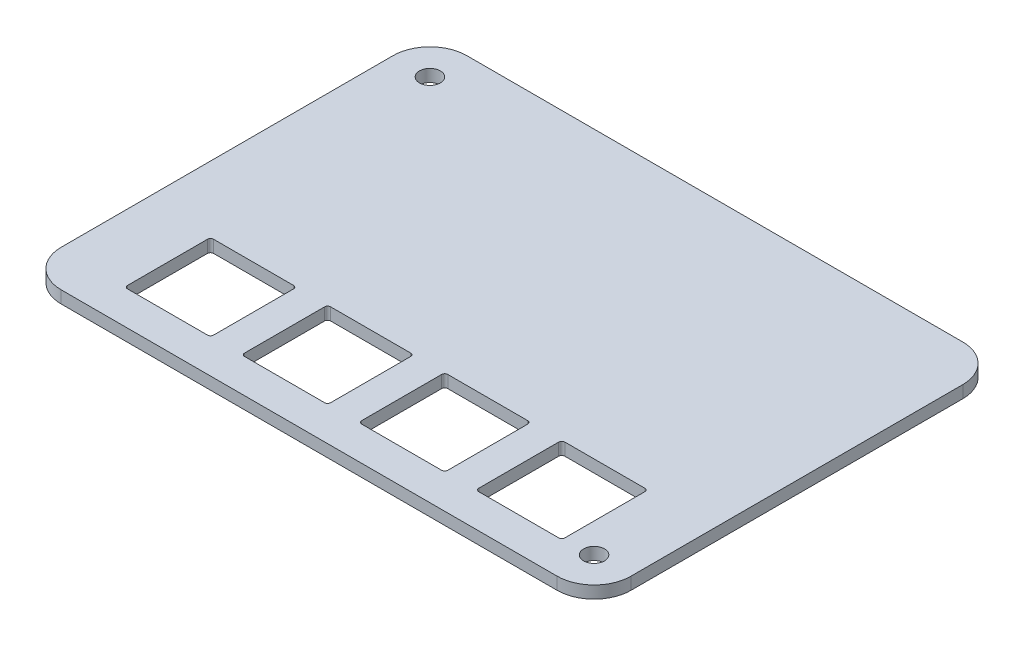
SolidWorks part; units mm, degrees
note: The reader was unsure of these and kept them because the rebuilt part matched: shared geometry of "Schizzo5<3>".
ref_plane "Piano frontale" through (0, 0, 0) normal (0, 0, 1) x (1, 0, 0)
ref_plane "Piano superiore" through (0, 0, 0) normal (0, 1, 0) x (1, 0, 0)
ref_plane "Piano destro" through (0, 0, 0) normal (1, 0, 0) x (0, 0, -1)
sketch "Schizzo1" plane through (0, 0, 0) normal (0, 1, 0) x (1, 0, 0)
  line L0 (0, 0) -> (0, 60)
  line L5 (0, 60) -> (-76.2, 60)
  line L6 (-76.2, 60) -> (-76.2, 0)
  line L8 (8.2513, -3) -> (-84.4513, -3)
  line L9 (8.2513, -3) -> (8.2513, 63)
  line L10 (8.2513, 63) -> (-84.4513, 63)
  line L11 (-84.4513, -3) -> (-84.4513, 63)
  line B0 (-76.2, 0) -> (0, 0)
  line B1 (-76.2, 19.05) -> (0, 19.05)
  line B2 (-73.175, 16.525) -> (-60.175, 16.525)
  line B3 (-73.175, 2.525) -> (-60.175, 2.525)
  line B4 (-73.675, 16.025) -> (-73.675, 3.025)
  line B5 (-59.675, 16.025) -> (-59.675, 3.025)
  line B6 (-54.125, 16.525) -> (-41.125, 16.525)
  line B7 (-54.125, 2.525) -> (-41.125, 2.525)
  line B8 (-54.625, 16.025) -> (-54.625, 3.025)
  line B9 (-40.625, 16.025) -> (-40.625, 3.025)
  line B10 (-35.075, 16.525) -> (-22.075, 16.525)
  line B11 (-35.075, 2.525) -> (-22.075, 2.525)
  line B12 (-35.575, 16.025) -> (-35.575, 3.025)
  line B13 (-21.575, 16.025) -> (-21.575, 3.025)
  line B14 (-16.025, 16.525) -> (-3.025, 16.525)
  line B15 (-16.025, 2.525) -> (-3.025, 2.525)
  line B16 (-16.525, 16.025) -> (-16.525, 3.025)
  line B17 (-2.525, 16.025) -> (-2.525, 3.025)
  line B18 (-76.2, 0) -> (-76.2, 19.05)
  line B19 (0, 0) -> (0, 19.05)
  arc B20 (-73.175, 16.525) -> (-73.675, 16.025) centre (-73.175, 16.025) ccw
  arc B21 (-59.675, 16.025) -> (-60.175, 16.525) centre (-60.175, 16.025) ccw
  arc B22 (-73.675, 3.025) -> (-73.175, 2.525) centre (-73.175, 3.025) ccw
  arc B23 (-60.175, 2.525) -> (-59.675, 3.025) centre (-60.175, 3.025) ccw
  arc B24 (-54.125, 16.525) -> (-54.625, 16.025) centre (-54.125, 16.025) ccw
  arc B25 (-40.625, 16.025) -> (-41.125, 16.525) centre (-41.125, 16.025) ccw
  arc B26 (-54.625, 3.025) -> (-54.125, 2.525) centre (-54.125, 3.025) ccw
  arc B27 (-41.125, 2.525) -> (-40.625, 3.025) centre (-41.125, 3.025) ccw
  arc B28 (-35.075, 16.525) -> (-35.575, 16.025) centre (-35.075, 16.025) ccw
  arc B29 (-21.575, 16.025) -> (-22.075, 16.525) centre (-22.075, 16.025) ccw
  arc B30 (-35.575, 3.025) -> (-35.075, 2.525) centre (-35.075, 3.025) ccw
  arc B31 (-22.075, 2.525) -> (-21.575, 3.025) centre (-22.075, 3.025) ccw
  arc B32 (-16.025, 16.525) -> (-16.525, 16.025) centre (-16.025, 16.025) ccw
  arc B33 (-2.525, 16.025) -> (-3.025, 16.525) centre (-3.025, 16.025) ccw
  arc B34 (-16.525, 3.025) -> (-16.025, 2.525) centre (-16.025, 3.025) ccw
  arc B35 (-3.025, 2.525) -> (-2.525, 3.025) centre (-3.025, 3.025) ccw
  dimension "D1" = 40.95
  dimension "D2" = 3
  dimension "D3" = 8.2513
  dimension "D4" = 3
  dimension "D5" = 8.2513
sketch_block_instance "plate-2026-10-07T17_50_42.415Z-1"
sketch_block "plate-2026-10-07T17_50_42.415Z"
extrude "Estrusione-Estrusione1" add sketch "Schizzo1" along normal blind 2 contours L6 B1 L0 L5 | B1 L6 B0 L0 B35 B15 B34 B16 B32 B14 B33 B17 B31 B11 B30 B12 B28 B10 B29 B13 B27 B7 B26 B8 B24 B6 B25 B9 B23 B3 B22 B4 B20 B2 B21 B5 | L11 L8 L9 L10 B0 L6 L5 L0
fillet "Raccordo1" radius 6 4 edges at (-84.4513, 1, 3) (8.2513, 1, 3) (8.2513, 1, -63) (-84.4513, 1, -63)
sketch "Schizzo2" plane through (0, 2, 0) normal (0, 1, 0) x (1, 0, 0)
  arc A2 (-78.4513, 63) -> (-84.4513, 57) centre (-78.4513, 57) ccw construction
  arc A3 (2.2513, -3) -> (8.2513, 3) centre (2.2513, 3) ccw construction
  point P0 (-78.4513, 57)
  point P2 (2.2513, 3)
  point P8 (0, 0)
  point P12 (0, 0)
  point P13 (0, 0)
  point P17 (0, 0)
  point P18 (0, 0)
hole_wizard "Foro per Vite M3-1" positions "Schizzo2" profile "Schizzo3" hole size "M3" standard "ISO"
sketch "Schizzo3" plane through (-78.4513, 2, -57) normal (1, 0, 0) x (0, 0, 1)
  line L0 (0, 0) -> (0, 14.0215)
  line L1 (0, 14.0215) -> (1.7, 13)
  line L2 (1.7, 13) -> (1.7, 0)
  line L5 (1.7, 0) -> (0, 0)
  line L10 (0, 14.0215) -> (-1.7, 13) construction
  line L11 (0, -6.35) -> (0, 107.95) construction
  dimension "Hole Dia." = 3.4
  dimension "Hole Depth" = 13
  dimension "Drill Angle" = 118
sketch "Schizzo5" plane through (0, 0, 0) normal (0, 1, 0) x (1, 0, 0)
  line L0 (-48.9354, 27.1805) -> (-52.2996, 33.9829)
  line L1 (-52.2996, 33.9829) -> (-53.1758, 36.2114)
  line L2 (-53.1758, 36.2114) -> (-53.1758, 36.5924)
  line L3 (-53.1758, 36.5924) -> (-52.2615, 37.44)
  line L4 (-46.252, 47.7543) -> (-48.6235, 50.4971)
  line L5 (-48.6235, 50.4971) -> (-49.5568, 51.6305)
  line L6 (-49.5568, 51.6305) -> (-49.8425, 51.859)
  line L7 (-49.8425, 51.859) -> (-49.9187, 52.1162)
  line L8 (-49.9187, 52.1162) -> (-49.2996, 52.5067)
  line L9 (-49.2996, 52.5067) -> (-47.7187, 53.3257)
  line L10 (-47.7187, 53.3257) -> (-46.0139, 54.0781)
  line L11 (-46.0139, 54.0781) -> (-45.5949, 54.2876)
  line L12 (-45.5949, 54.2876) -> (-45.252, 54.1067)
  line L13 (-45.252, 54.1067) -> (-45.3854, 54.0209)
  line L14 (-45.3854, 54.0209) -> (-46.7568, 53.44)
  line L15 (-46.7568, 53.44) -> (-48.1663, 52.8209)
  line L16 (-48.1663, 52.8209) -> (-48.3568, 52.6305)
  line L17 (-48.3568, 52.6305) -> (-48.8711, 52.3638)
  line L18 (-48.8711, 52.3638) -> (-48.8711, 52.259)
  line L19 (-48.8711, 52.259) -> (-48.233, 52.2114)
  line L20 (-48.233, 52.2114) -> (-46.7663, 52.2495)
  line L21 (-46.7663, 52.2495) -> (-44.8901, 52.3352)
  line L22 (-44.8901, 52.3352) -> (-43.5282, 52.5448)
  line L23 (-43.5282, 52.5448) -> (-43.3568, 54.1733)
  line L24 (-43.3568, 54.1733) -> (-42.9854, 53.9543)
  line L25 (-42.9854, 53.9543) -> (-43.1473, 52.7543)
  line L26 (-43.1473, 52.7543) -> (-43.0806, 52.6495)
  line L27 (-43.0806, 52.6495) -> (-41.7854, 52.8019)
  line L28 (-40.7568, 52.9924) -> (-39.1473, 53.459)
  line L29 (-39.1473, 53.459) -> (-38.0901, 53.7924)
  line L30 (-38.0901, 53.7924) -> (-37.6996, 53.8971)
  line L31 (-37.6996, 53.8971) -> (-36.3568, 54.3829)
  line L32 (-36.3568, 54.3829) -> (-35.0235, 52.3733)
  line L33 (-35.0806, 54.9543) -> (-34.433, 55.1067)
  line L34 (-34.433, 55.1067) -> (-32.8806, 55.6686)
  line L35 (-32.8806, 55.6686) -> (-31.652, 56.1352)
  line L36 (-31.652, 56.1352) -> (-31.0615, 56.5162)
  line L37 (-31.0615, 56.5162) -> (-30.052, 57.0209)
  line L38 (-30.052, 57.0209) -> (-29.5187, 57.3829)
  line L39 (-29.5187, 57.3829) -> (-29.5568, 57.5448)
  line L40 (-29.5568, 57.5448) -> (-29.7949, 57.5829)
  line L41 (-29.7949, 57.5829) -> (-31.9758, 57.4733)
  line L42 (-31.9758, 57.4733) -> (-33.5139, 57.3686)
  line L43 (-33.5139, 57.3686) -> (-34.7187, 57.1257)
  line L44 (-34.7187, 57.1257) -> (-35.7139, 56.9067)
  line L45 (-35.7139, 56.9067) -> (-36.733, 56.7067)
  line L46 (-36.733, 56.7067) -> (-38.6711, 56.1448)
  line L47 (-38.6711, 56.1448) -> (-39.1092, 56.0876)
  line L48 (-39.1092, 56.0876) -> (-39.9282, 55.8448)
  line L49 (-39.9282, 55.8448) -> (-40.1615, 55.7495)
  line L50 (-40.1615, 55.7495) -> (-41.2425, 55.4638)
  line L51 (-41.2425, 55.4638) -> (-42.452, 55.0924)
  line L52 (-42.452, 55.0924) -> (-42.4615, 53.8114)
  line L53 (-42.4615, 53.8114) -> (-42.5282, 53.7876)
  line L54 (-42.5282, 53.7876) -> (-42.7092, 53.8543)
  line L55 (-42.7092, 53.8543) -> (-42.7377, 53.9352)
  line L56 (-42.7377, 53.9352) -> (-42.7235, 54.5352)
  line L57 (-42.7235, 54.5352) -> (-42.833, 55.2257)
  line L58 (-42.833, 55.2257) -> (-42.552, 55.3162)
  line L59 (-42.552, 55.3162) -> (-42.1711, 55.5352)
  line L60 (-42.1711, 55.5352) -> (-41.9187, 55.5733)
  line L61 (-41.9187, 55.5733) -> (-41.4615, 55.7495)
  line L62 (-41.4615, 55.7495) -> (-41.1615, 55.7829)
  line L63 (-41.1615, 55.7829) -> (-38.2806, 56.6638)
  line L64 (-38.2806, 56.6638) -> (-35.9473, 57.1305)
  line L65 (-35.9473, 57.1305) -> (-33.2473, 57.759)
  line L66 (-33.2473, 57.759) -> (-30.7235, 57.9733)
  line L67 (-30.7235, 57.9733) -> (-30.0901, 58.059)
  line L68 (-30.0901, 58.059) -> (-28.8187, 57.9971)
  line L69 (-28.8187, 57.9971) -> (-28.6568, 57.9019)
  line L70 (-28.6568, 57.9019) -> (-28.7758, 57.6209)
  line L71 (-28.7758, 57.6209) -> (-28.8044, 57.3829)
  line L72 (-28.8044, 57.3829) -> (-29.0996, 56.5352)
  line L73 (-29.0996, 56.5352) -> (-29.5425, 55.4448)
  line L74 (-29.5425, 55.4448) -> (-29.8663, 54.6829)
  line L75 (-29.8663, 54.6829) -> (-30.1473, 53.8448)
  line L76 (-30.1473, 53.8448) -> (-30.5187, 52.6543)
  line L77 (-30.5187, 52.6543) -> (-30.8901, 51.2733)
  line L78 (-30.8901, 51.2733) -> (-31.0854, 50.559)
  line L79 (-31.0854, 50.559) -> (-31.2568, 50.0781)
  line L80 (-31.2568, 50.0781) -> (-31.3092, 49.7257)
  line L81 (-31.3092, 49.7257) -> (-31.5377, 48.9876)
  line L82 (-31.5377, 48.9876) -> (-31.7663, 47.9257)
  line L83 (-31.7663, 47.9257) -> (-32.0139, 46.3209)
  line L84 (-32.0139, 46.3209) -> (-31.9044, 46.2781)
  line L85 (-31.9044, 46.2781) -> (-30.452, 44.7924)
  line L86 (-30.452, 44.7924) -> (-29.3139, 43.8352)
  line L87 (-29.3139, 43.8352) -> (-27.4615, 42.24)
  line L88 (-27.4615, 42.24) -> (-24.7425, 40.2067)
  line L89 (-24.7425, 40.2067) -> (-22.652, 38.6448)
  line L90 (-22.652, 38.6448) -> (-22.5949, 38.3638)
  line L91 (-22.5949, 38.3638) -> (-22.6949, 38.1019)
  line L92 (-22.6949, 38.1019) -> (-22.9282, 37.34)
  line L93 (-22.9282, 37.34) -> (-23.0996, 36.6829)
  line L94 (-23.0996, 36.6829) -> (-23.1854, 36.3067)
  line L95 (-23.1854, 36.3067) -> (-23.3806, 35.7257)
  line L96 (-23.3806, 35.7257) -> (-23.6711, 35.0305)
  line L97 (-23.6711, 35.0305) -> (-24.2568, 33.3543)
  line L98 (-24.2568, 33.3543) -> (-24.4806, 32.7305)
  line L99 (-24.4806, 32.7305) -> (-24.7473, 32.2543)
  line L100 (-24.7473, 32.2543) -> (-25.1092, 31.4162)
  line L101 (-25.1092, 31.4162) -> (-25.6758, 30.0971)
  line L102 (-25.6758, 30.0971) -> (-26.6568, 28.2733)
  line L103 (-26.6568, 28.2733) -> (-27.3139, 27.2209)
  line L104 (-27.3139, 27.2209) -> (-27.5615, 26.7781)
  line L105 (-27.5615, 26.7781) -> (-28.2282, 25.7019)
  line L106 (-28.2282, 25.7019) -> (-28.3996, 25.4305)
  line L107 (-28.3996, 25.4305) -> (-28.6187, 25.1924)
  line L108 (-28.6187, 25.1924) -> (-29.1377, 24.459)
  line L109 (-29.1377, 24.459) -> (-29.8139, 23.6876)
  line L110 (-29.8139, 23.6876) -> (-30.5663, 23.459)
  line L111 (-30.5663, 23.459) -> (-32.8806, 23.2495)
  line L112 (-32.8806, 23.2495) -> (-36.1187, 22.9829)
  line L113 (-36.1187, 22.9829) -> (-37.7568, 22.9257)
  line L114 (-37.7568, 22.9257) -> (-43.3235, 22.7305)
  line L115 (-43.3235, 22.7305) -> (-45.4996, 22.9543)
  line L116 (-45.4996, 22.9543) -> (-45.9235, 23.0305)
  line L117 (-45.9235, 23.0305) -> (-46.1735, 23.2019)
  line L118 (-46.1735, 23.2019) -> (-46.9996, 24.2733)
  line L119 (-46.9996, 24.2733) -> (-47.7473, 25.3281)
  line L120 (-47.7473, 25.3281) -> (-48.4377, 26.3448)
  line L121 (-48.4377, 26.3448) -> (-48.9354, 27.1805)
  line L122 (-46.6711, 26.9448) -> (-46.5377, 27.3209)
  line L123 (-46.5377, 27.3209) -> (-46.2949, 27.6971)
  line L124 (-46.2949, 27.6971) -> (-45.2139, 29.6114)
  line L125 (-45.2139, 29.6114) -> (-43.9377, 31.7638)
  line L126 (-43.9377, 31.7638) -> (-43.3044, 32.7019)
  line L127 (-43.3044, 32.7019) -> (-43.0663, 33.0781)
  line L128 (-43.0663, 33.0781) -> (-42.8139, 33.659)
  line L129 (-42.8139, 33.659) -> (-42.6806, 34.2924)
  line L130 (-42.6806, 34.2924) -> (-41.6568, 37.7686)
  line L131 (-41.6568, 37.7686) -> (-40.9806, 39.74)
  line L132 (-40.9806, 39.74) -> (-40.6377, 40.8876)
  line L133 (-40.6377, 40.8876) -> (-39.7949, 43.6114)
  line L134 (-39.7949, 43.6114) -> (-39.4854, 43.7829)
  line L135 (-38.1235, 44.0924) -> (-37.4568, 44.2067)
  line L136 (-36.1377, 44.3543) -> (-36.0282, 44.3162)
  line L137 (-36.0282, 44.3162) -> (-35.2377, 41.24)
  line L138 (-35.2377, 41.24) -> (-34.6139, 39.0305)
  line L139 (-34.6139, 39.0305) -> (-34.2282, 38.059)
  line L140 (-34.2282, 38.059) -> (-34.0282, 37.4448)
  line L141 (-34.0282, 37.4448) -> (-33.9092, 36.9829)
  line L142 (-33.9092, 36.9829) -> (-33.4139, 35.7733)
  line L143 (-33.4139, 35.7733) -> (-33.3377, 35.3209)
  line L144 (-33.3377, 35.3209) -> (-32.7139, 33.9448)
  line L145 (-32.7139, 33.9448) -> (-32.0139, 32.5733)
  line L146 (-32.0139, 32.5733) -> (-30.8187, 30.2257)
  line L147 (-30.8187, 30.2257) -> (-29.6996, 27.9162)
  line L148 (-29.6996, 27.9162) -> (-29.5949, 27.5924)
  line L149 (-29.5949, 27.5924) -> (-29.4806, 27.5067)
  line L150 (-29.4806, 27.5067) -> (-29.5282, 27.3305)
  line L151 (-29.5282, 27.3305) -> (-29.8568, 26.859)
  line L152 (-30.4615, 26.2114) -> (-31.1996, 25.6733)
  line L153 (-31.1996, 25.6733) -> (-31.8139, 25.2924)
  line L154 (-31.8139, 25.2924) -> (-32.633, 24.8448)
  line L155 (-32.633, 24.8448) -> (-32.8615, 24.7495)
  line L156 (-35.4949, 24.4781) -> (-37.1282, 24.5876)
  line L157 (-37.1282, 24.5876) -> (-37.2615, 24.7067)
  line L158 (-37.2615, 24.7067) -> (-37.4187, 27.7257)
  line L159 (-37.4187, 27.7257) -> (-37.5758, 29.7257)
  line L160 (-37.5758, 29.7257) -> (-37.5663, 31.3686)
  line L161 (-37.5663, 31.3686) -> (-37.7235, 32.5733)
  line L162 (-37.7235, 32.5733) -> (-37.7758, 32.9448)
  line L163 (-37.7758, 32.9448) -> (-39.9044, 32.9733)
  line L164 (-39.9044, 32.9733) -> (-39.8139, 32.2638)
  line L165 (-39.8139, 32.2638) -> (-39.9092, 31.2448)
  line L166 (-39.9092, 31.2448) -> (-40.0854, 30.7067)
  line L167 (-40.0854, 30.7067) -> (-40.1282, 29.9067)
  line L168 (-40.1282, 29.9067) -> (-40.3615, 28.7543)
  line L169 (-40.3615, 28.7543) -> (-40.5425, 27.6257)
  line L170 (-40.5425, 27.6257) -> (-40.6901, 26.2448)
  line L171 (-40.6901, 26.2448) -> (-40.9187, 24.8209)
  line L172 (-40.9187, 24.8209) -> (-41.0377, 24.459)
  line L173 (-41.0377, 24.459) -> (-43.652, 24.0638)
  line L174 (-43.652, 24.0638) -> (-43.9235, 24.2067)
  line L175 (-37.5504, 35.2908) -> (-38.052, 35.4876)
  line L176 (-38.052, 35.4876) -> (-39.0171, 35.9575)
  line L177 (-39.5885, 36.4146) -> (-38.6742, 41.7225)
  line L178 (-38.6742, 41.7225) -> (-38.579, 41.6082)
  line L179 (-38.579, 41.6082) -> (-38.3377, 40.7257)
  line L180 (-38.3377, 40.7257) -> (-38.1917, 39.6082)
  line L181 (-38.1917, 39.6082) -> (-37.5504, 35.8178)
  line L182 (-37.5504, 35.8178) -> (-37.4615, 35.5511)
  line L183 (-37.4615, 35.5511) -> (-37.5187, 35.3606)
  line L184 (-37.5187, 35.3606) -> (-37.5504, 35.2908)
  spline S0 degree 2 poles (-52.2615, 37.44) (-47.852, 41.4781) (-47.8044, 41.5733) knots 4 4 4 5 5 5
  spline S1 degree 3 poles (-47.8044, 41.5733) (-47.7568, 41.6686) (-45.2901, 43.6686) (-45.233, 43.7638) knots 5 5 5 5 6 6 6 6
  spline S2 degree 2 poles (-45.233, 43.7638) (-45.1758, 43.859) (-44.2996, 44.6686) knots 6 6 6 7 7 7
  spline S3 degree 2 poles (-44.2996, 44.6686) (-44.8425, 45.8114) (-44.8901, 45.8305) knots 7 7 7 8 8 8
  spline S4 degree 2 poles (-44.8901, 45.8305) (-44.9377, 45.8495) (-46.252, 47.7543) knots 8 8 8 9 9 9
  spline S5 degree 2 poles (-41.7854, 52.8019) (-41.0615, 53.0114) (-41.033, 53.0114) knots 33 33 33 34 34 34
  spline S6 degree 2 poles (-41.033, 53.0114) (-41.0044, 53.0114) (-40.7568, 52.9924) knots 34 34 34 35 35 35
  spline S7 degree 2 poles (-35.0235, 52.3733) (-35.033, 53.6495) (-35.052, 53.6971) knots 40 40 40 41 41 41
  spline S8 degree 3 poles (-35.052, 53.6971) (-35.0711, 53.7448) (-35.2139, 54.5829) (-35.2139, 54.6114) knots 41 41 41 41 42 42 42 42
  spline S9 degree 2 poles (-35.2139, 54.6114) (-35.2139, 54.64) (-35.0806, 54.9543) knots 42 42 42 43 43 43
  spline S10 degree 2 poles (-39.4854, 43.7829) (-38.952, 43.94) (-38.9282, 43.94) knots 13 13 13 14 14 14
  spline S11 degree 2 poles (-38.9282, 43.94) (-38.9044, 43.94) (-38.1235, 44.0924) knots 14 14 14 15 15 15
  spline S12 degree 2 poles (-37.4568, 44.2067) (-36.6901, 44.3543) (-36.6663, 44.3543) knots 16 16 16 17 17 17
  spline S13 degree 2 poles (-36.6663, 44.3543) (-36.6425, 44.3543) (-36.1377, 44.3543) knots 17 17 17 18 18 18
  spline S14 degree 2 poles (-29.8568, 26.859) (-29.9425, 26.6495) (-29.9568, 26.6543) knots 34 34 34 35 35 35
  spline S15 degree 2 poles (-29.9568, 26.6543) (-29.9711, 26.659) (-30.4615, 26.2114) knots 35 35 35 36 36 36
  spline S16 degree 2 poles (-32.8615, 24.7495) (-34.033, 24.54) (-34.0615, 24.5495) knots 40 40 40 41 41 41
  spline S17 degree 2 poles (-34.0615, 24.5495) (-34.0901, 24.559) (-35.4949, 24.4781) knots 41 41 41 42 42 42
  spline S18 degree 2 poles (-43.9235, 24.2067) (-44.7854, 25.1971) (-44.8092, 25.2067) knots 61 61 61 62 62 62
  spline S19 degree 3 poles (-44.8092, 25.2067) (-44.833, 25.2162) (-46.0568, 26.3495) (-46.0758, 26.359) knots 62 62 62 62 63 63 63 63
  spline S20 degree 2 poles (-46.0758, 26.359) (-46.0949, 26.3686) (-46.6711, 26.9448) knots 63 63 63 64 64 64
  spline S21 degree 2 poles (-39.0171, 35.9575) (-39.4298, 36.1606) (-39.4425, 36.1924) knots 2 2 2 3 3 3
  spline S22 degree 2 poles (-39.4425, 36.1924) (-39.4552, 36.2241) (-39.5885, 36.4146) knots 3 3 3 4 4 4
extrude "Taglio-Estrusione1" cut sketch "Schizzo5" along normal blind 1 contours S19 S20 L122 L123 L124 L125 L126 L127 L128 L129 L130 L131 L132 L133 L134 S10 S11 L135 S12 S13 L136 L137 L138 L139 L140 L141 L142 L143 L144 L145 L146 L147 L148 L149 L150 L151 S14 S15 L152 L153 L154 L155 S16 S17 L156 L157 L158 L159 L160 L161 L162
extrude "Estrusione-Estrusione2" add sketch "Schizzo5<3>" against normal blind 1 contours S8 S9 L33 L34 L35 L36 L37 L38 L39 L40 L41 L42 L43 L44 L45 L46 L47 L48 L49 L50 L51 L52 L53 L54 L55 L56 L57 L58 L59 L60 L61 L62 L63 L64 L65 L66 L67 L68 L69 L70 L71 L72 L73 L74 L75 L76 L77 L78 L79 L80 L81
sketch "Schizzo5<3>" plane through (0, 0, 0) normal (0, 1, 0) x (1, 0, 0) same geometry as "Schizzo5"
